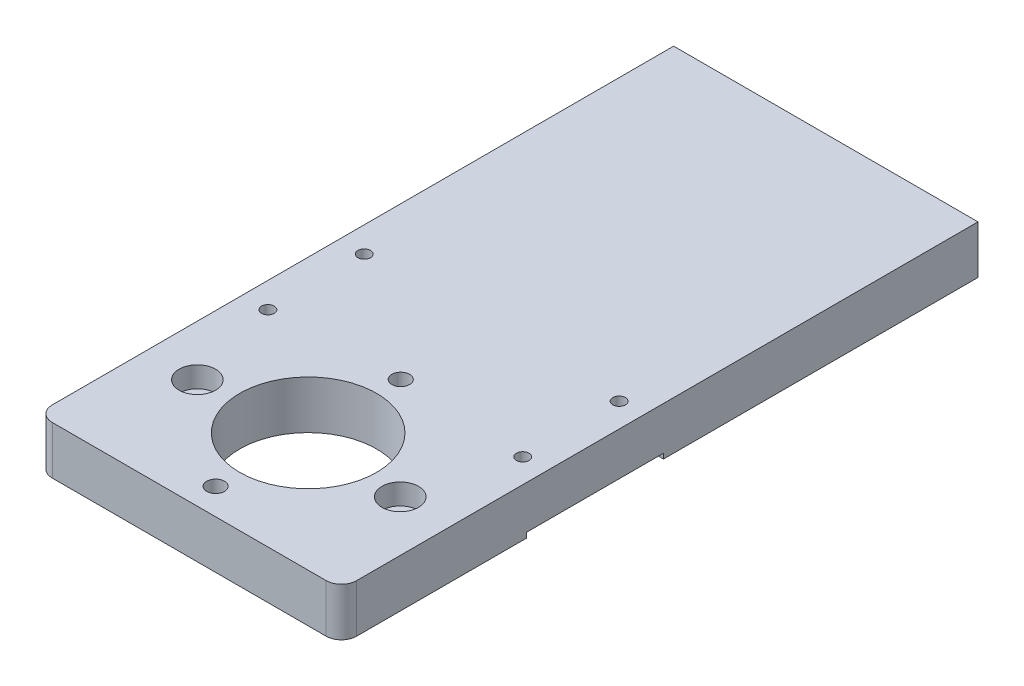
SolidWorks part; units mm, degrees
ref_plane "前视基准面" through (0, 0, 0) normal (0, 0, 1) x (1, 0, 0)
ref_plane "上视基准面" through (0, 0, 0) normal (0, 1, 0) x (1, 0, 0)
ref_plane "右视基准面" through (0, 0, 0) normal (1, 0, 0) x (0, 0, -1)
sketch "草图1" plane through (0, 0, 0) normal (0, 1, 0) x (1, 0, 0)
  line L1 (-30, 31.75) -> (30, 31.75)
  line L2 (-30, 31.75) -> (-30, -31.75)
  line L3 (-30, -31.75) -> (30, -31.75)
  line L4 (30, 31.75) -> (30, -31.75)
  line L5 (-30, 31.75) -> (30, -31.75) construction
  line L6 (-30, -31.75) -> (30, 31.75) construction
  point P0 (0, 0)
  dimension "D1" = 60
  dimension "D2" = 63.5
extrude "凸台-拉伸1" add sketch "草图1" along normal blind 9.5
fillet "圆角1" radius 3 2 edges at (30, 4.75, 31.75) (-30, 4.75, 31.75)
sketch "草图3" plane through (0, 9.5, 0) normal (0, 1, 0) x (1, 0, 0)
  circle A0 centre (0, -8.3029) radius 13.5
  dimension "D1" = 27
extrude "切除-拉伸2" cut sketch "草图3" against normal through all
sketch "草图4" plane through (0, 0, 0) normal (0, -1, 0) x (1, 0, 0)
  line L1 (20.5, -4.75) -> (30, -4.75)
  line L2 (20.5, -7.25) -> (20.5, -31.75)
  line L3 (20.5, -31.75) -> (30, -31.75)
  line L4 (30, -4.75) -> (30, -31.75)
  line L5 (-20.5, -4.75) -> (-30, -4.75)
  line L6 (-20.5, -7.25) -> (-20.5, -31.75)
  line L7 (-20.5, -31.75) -> (-30, -31.75)
  line L8 (-30, -4.75) -> (-30, -31.75)
  arc A1 (-20.5, -7.25) -> (-20.5, -4.75) centre (-20.5, -6) ccw
  arc A4 (20.5, -4.75) -> (20.5, -7.25) centre (20.5, -6) ccw
  dimension "D1" = 2.5
  dimension "D2" = 2.5
extrude "切除-拉伸3" cut sketch "草图4" against normal blind 1
sketch "草图5" plane through (0, 9.5, 0) normal (0, 1, 0) x (1, 0, 0)
  circle A0 centre (25.25, 27.75) radius 1.25
  circle A1 centre (25.25, 8.75) radius 1.25
  circle A2 centre (-25, 27.75) radius 1.25
  circle A3 centre (-25, 8.75) radius 1.25
  dimension "D1" = 2.5
extrude "切除-拉伸4" cut sketch "草图5" against normal through all
sketch "草图7" plane through (0, 0, 0) normal (0, -1, 0) x (1, 0, 0)
  circle A0 centre (-20, 10.15) radius 4
  circle A1 centre (20, 10.15) radius 4
  dimension "D1" = 8
extrude "切除-拉伸6" cut sketch "草图7" against normal blind 1
sketch "草图8" plane through (0, 9.5, 0) normal (0, 1, 0) x (1, 0, 0)
  circle A0 centre (-20, -10.15) radius 2
  circle A1 centre (20, -10.15) radius 2
  dimension "D1" = 4
extrude "切除-拉伸7" cut sketch "草图8" against normal through all
sketch "草图9" plane through (0, 9.5, 0) normal (0, 1, 0) x (1, 0, 0)
  circle A0 centre (-20, -10.15) radius 3.6
  circle A1 centre (20, -10.15) radius 3.6
  dimension "D1" = 7.2
extrude "切除-拉伸8" cut sketch "草图9" against normal blind 4.1
sketch "草图10" plane through (0, 9.5, 0) normal (0, 1, 0) x (1, 0, 0)
  circle A0 centre (0, 9.9471) radius 1.75
  circle A1 centre (0, -26.5529) radius 1.75
  dimension "D1" = 3.5
extrude "切除-拉伸9" cut sketch "草图10" against normal through all
sketch "草图11" plane through (0, 9.5, 0) normal (0, 1, 0) x (1, 0, 0)
  line L1 (-30, 31.75) -> (30, 31.75)
  line L2 (-30, 31.75) -> (-30, 93.75)
  line L3 (-30, 93.75) -> (30, 93.75)
  line L4 (30, 31.75) -> (30, 93.75)
  dimension "D1" = 62
  dimension "D2" = 60
extrude "凸台-拉伸2" add sketch "草图11" against normal blind 9.5
ref_plane "基准面1" through (0, 0, 0) normal (1, 0, 0) x (0, 0, -1)
